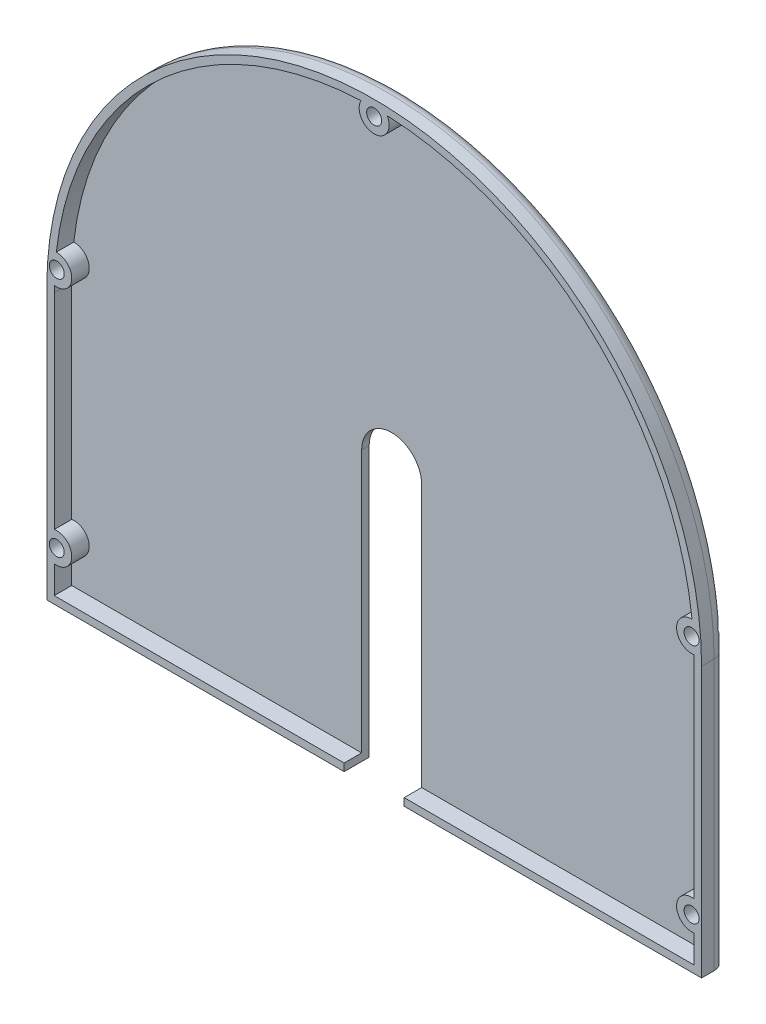
SolidWorks part; units mm, degrees
ref_plane "Front Plane" through (0, 0, 0) normal (0, 0, 1) x (1, 0, 0)
ref_plane "Top Plane" through (0, 0, 0) normal (0, 1, 0) x (1, 0, 0)
ref_plane "Right Plane" through (0, 0, 0) normal (1, 0, 0) x (0, 0, -1)
sketch "Sketch3" plane through (0, 0, 0) normal (0, 0, 1) x (1, 0, 0)
  line L1 (-65.5, 27) -> (65.5, 27)
  line L2 (-65.5, 27) -> (-65.5, -27)
  line L3 (-65.5, -27) -> (65.5, -27)
  line L4 (65.5, 27) -> (65.5, -27)
  line L5 (-65.5, 27) -> (65.5, -27) construction
  line L6 (-65.5, -27) -> (65.5, 27) construction
  arc A1 (65.5, 27) -> (-65.5, 27) centre (0, 27) ccw
  point P0 (0, 0)
  dimension "D1" = 131
  dimension "D2" = 54
extrude "Boss-Extrude2" add sketch "Sketch3" along normal blind 5 contours L1 A1 | L4 L1 L2 L3
hole_wizard "Ø3.0 (3) Diameter Hole1" positions "Sketch4" profile "Sketch5" hole size "Ø3.0" standard "AS"
sketch "Sketch4" plane through (0, 0, 5) normal (0, 0, 1) x (1, 0, 0)
  line L0 (-65.5, -27) -> (65.5, -27) construction
  line L1 (-65.5, 27) -> (-65.5, -27) construction
  line L2 (65.5, 27) -> (65.5, -27) construction
  arc A1 (65.5, 27) -> (-65.5, 27) centre (0, 27) ccw construction
  point P0 (-63.5, -17)
  point P2 (63.5, -17)
  point P4 (0, 89.5)
  point P6 (63.5, 31.2101)
  point P8 (-63.5, 31.2101)
  dimension "D1" = 10
  dimension "D2" = 2
  dimension "D3" = 2
  dimension "D4" = 2
  dimension "D5" = 2
  dimension "D6" = 10
  dimension "D7" = 62.5
sketch "Sketch5" plane through (-63.5, -17, 5) normal (1, 0, 0) x (0, -1, 0)
  line L0 (0, 0) -> (0, 20.9013)
  line L1 (0, 20.9013) -> (1.5, 20)
  line L2 (1.5, 20) -> (1.5, 0)
  line L5 (1.5, 0) -> (0, 0)
  line L10 (0, 20.9013) -> (-1.5, 20) construction
  line L11 (0, -6.35) -> (0, 107.95) construction
  dimension "Hole Dia." = 3
  dimension "Hole Depth" = 20
  dimension "Drill Angle" = 118
shell "Shell1" thickness 1.5
sketch "Sketch6" plane through (0, 0, 0) normal (0, 0, -1) x (-1, 0, 0)
  line L0 (-6, 27) -> (-6, -27)
  line L1 (65.5, -27) -> (-65.5, -27) construction
  line L3 (6, -27) -> (6, 27)
  line L4 (-6, -27) -> (6, -27)
  arc A0 (6, 27) -> (-6, 27) centre (0, 27) ccw
  dimension "D1" = 12
extrude "Cut-Extrude1" cut sketch "Sketch6" against normal through all
fillet "Fillet2" radius 2.5 3 edges at (65.5, 0, 0) (-65.5, 0, 0) (0, 92.5, 0)
